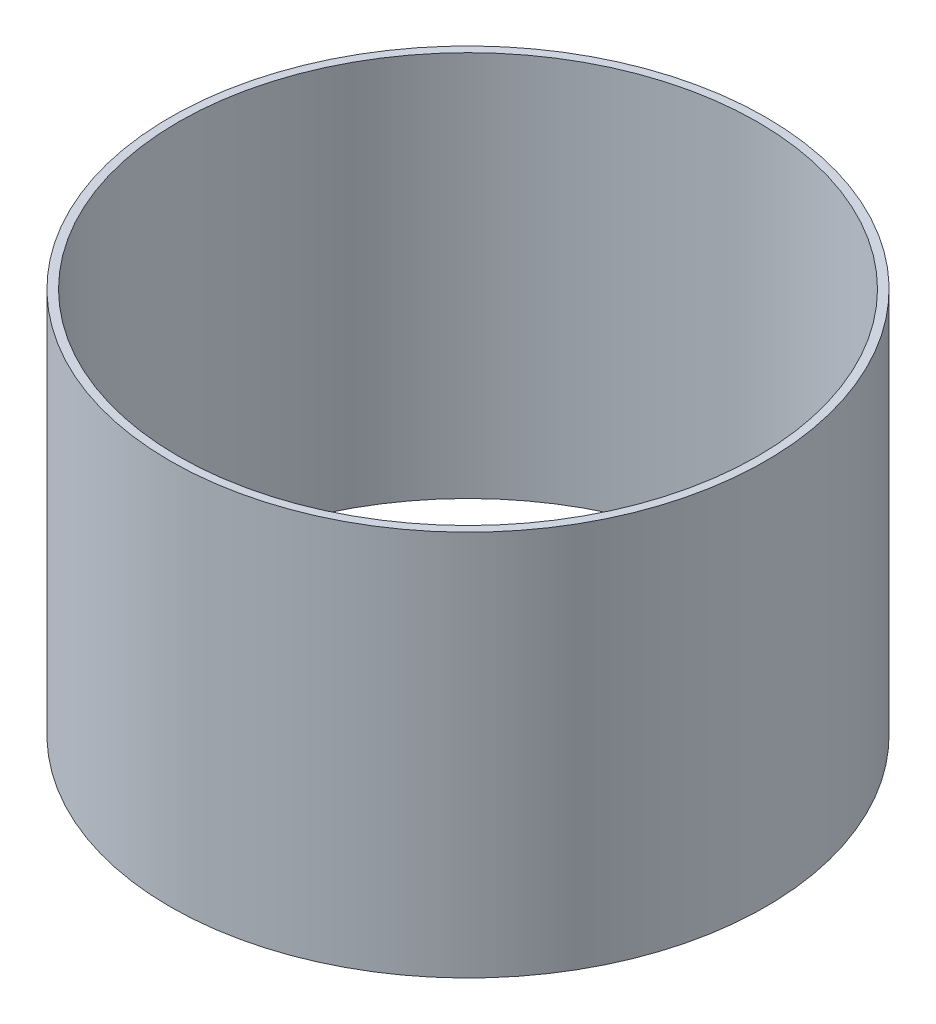
SolidWorks part; units mm, degrees
material "E-Glass Fiber"
ref_plane "Front Plane" through (0, 0, 0) normal (0, 0, 1) x (1, 0, 0)
ref_plane "Top Plane" through (0, 0, 0) normal (0, 1, 0) x (1, 0, 0)
ref_plane "Right Plane" through (0, 0, 0) normal (1, 0, 0) x (0, 0, -1)
sketch "Body Tube Profile" plane through (0, 0, 0) normal (0, 1, 0) x (1, 0, 0)
  circle A0 centre (0, 0) radius 76.2
  circle A1 centre (0, 0) radius 78.359
  dimension "D1" = 152.4
  dimension "D2" = 156.718
extrude "Body Tube Extrustion" add sketch "Body Tube Profile" along normal blind 101.6
equation "\"Length\"=4"
equation "\"Outer Diameter\"= 6.17"
equation "\"Inner Diameter\"= 6"
equation "\"Wall Thickness\"= 0.085"
equation "\"D1@Body Tube Profile\" = \"Inner Diameter\""
equation "\"D2@Body Tube Profile\" = \"Outer Diameter\""
equation "\"D1@Body Tube Extrustion\" = \"Length\""
